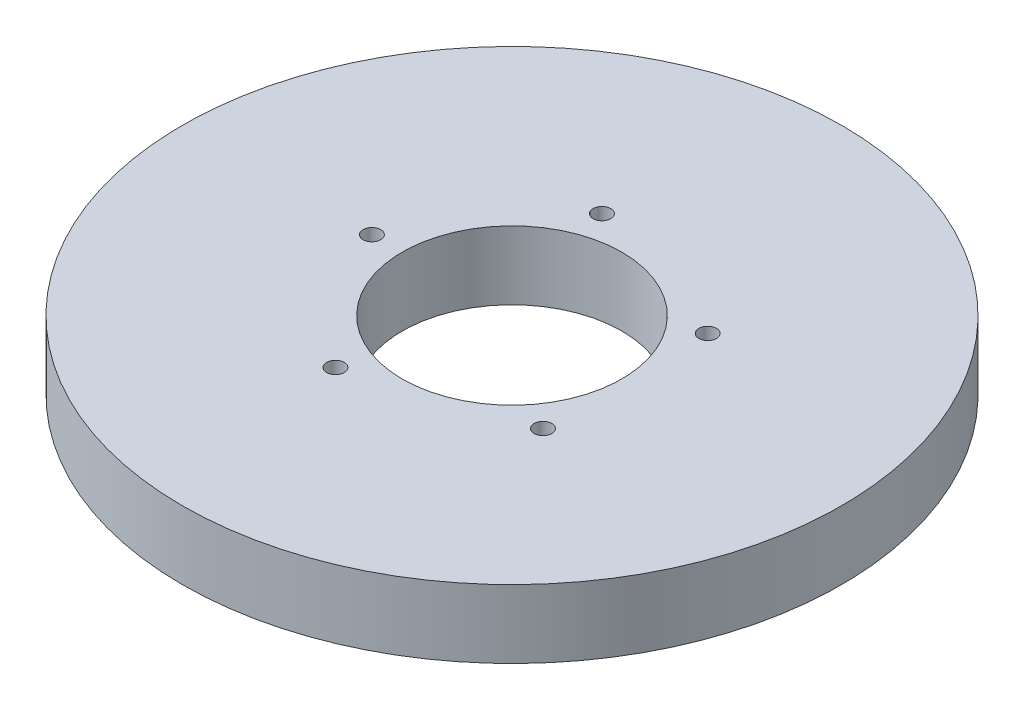
SolidWorks part; units mm, degrees
ref_plane "Front Plane" through (0, 0, 0) normal (0, 0, 1) x (1, 0, 0)
ref_plane "Top Plane" through (0, 0, 0) normal (0, 1, 0) x (1, 0, 0)
ref_plane "Right Plane" through (0, 0, 0) normal (1, 0, 0) x (0, 0, -1)
sketch "Sketch1" plane through (0, 0, 0) normal (0, 1, 0) x (1, 0, 0)
  circle A0 centre (0, 0) radius 67.5
  dimension "FLANGE_OD" = 135
extrude "Boss-Extrude1" add sketch "Sketch1" along normal blind 14
sketch "Sketch2" plane through (0, 0, 0) normal (0, 1, 0) x (1, 0, 0)
  circle A0 centre (0, 0) radius 22.5
  dimension "BORE_D" = 45
extrude "Cut-Extrude1" cut sketch "Sketch2" along normal through all
sketch "Sketch3" plane through (0, 14, 0) normal (0, 1, 0) x (1, 0, 0)
  circle A0 centre (0, 0) radius 28.6926 construction
  circle A1 centre (-28.6926, 0) radius 1.8007
  dimension "BOLT_D" = 3.6014
  dimension "BOLT_PCD" = 57.3852
extrude "Cut-Extrude2" cut sketch "Sketch3" against normal blind 12.5966
pattern_circular "CirPattern1" count 5 over 360 about axis through (0, 0, 0) along (0, 1, 0) of "Cut-Extrude2"
